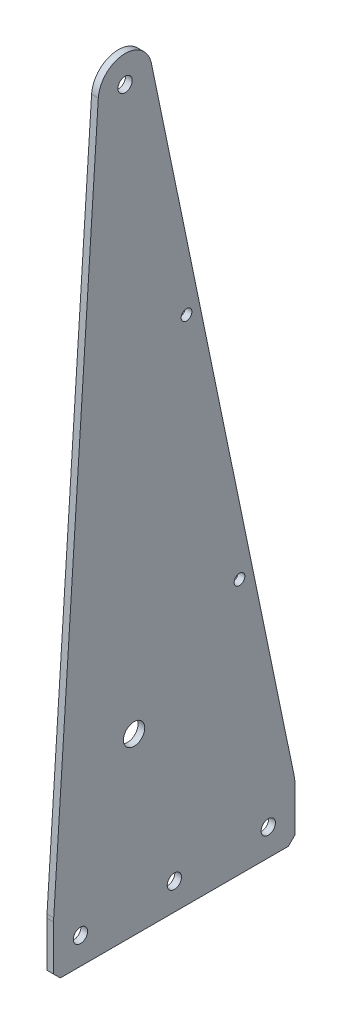
SolidWorks part; units mm, degrees
material "6061-T6 (SS)"
ref_plane "Front" through (0, 0, 0) normal (0, 0, 1) x (1, 0, 0)
ref_plane "Top" through (0, 0, 0) normal (0, 1, 0) x (1, 0, 0)
ref_plane "Right" through (0, 0, 0) normal (1, 0, 0) x (0, 0, -1)
sketch "Sketch1" plane through (0, 0, 0) normal (1, 0, 0) x (0, 0, -1)
  line L5 (63.5, 82.55) -> (-348.9452, 11.9126) construction
  line L6 (63.5, 82.55) -> (-7.1374, 494.9952) construction
  line L7 (59.2324, 350.8928) -> (22.2931, 141.3996) construction
  line L8 (22.2931, 141.3996) -> (4.6504, 41.3431) construction
  line L9 (63.5, 82.55) -> (4.6504, 41.3431) construction
  line L10 (4.6504, 41.3431) -> (-0.5288, 71.5841) construction
  line L11 (63.5, 82.55) -> (22.2931, 141.3996) construction
  line L12 (22.2931, 141.3996) -> (52.5341, 146.5788) construction
  circle A0 centre (63.5, 82.55) radius 5.0419
  dimension "D1" = 10.0838
  dimension "D3" = 63.5
  dimension "D2" = 82.55
  dimension "D4" = 80
  dimension "D7" = 70.6374
  dimension "D8" = 412.4452
  dimension "D9" = 90
  dimension "D10" = 101.6
  dimension "D11" = 212.725
sketch "Sketch2" plane through (0, 0, 0) normal (1, 0, 0) x (0, 0, -1)
  line L0 (25.4, 0) -> (25.4, 25.4)
  line L2 (25.4, 0) -> (139.7, 0)
  line L3 (139.7, 0) -> (139.7, 25.4)
  line L4 (139.7, 25.4) -> (71.6678, 353.4715)
  line L6 (25.4, 25.4) -> (46.559, 351.7146)
  arc A0 (71.6678, 353.4715) -> (46.559, 351.7146) centre (59.2324, 350.8928) ccw
  circle A2 centre (63.5, 82.55) radius 5.0419 construction
  circle A3 centre (63.5, 82.55) radius 5.0419
  circle A4 centre (59.2324, 350.8928) radius 3.3782
  dimension "D3" = 12.7
  dimension "D4" = 6.7564
  dimension "D5" = 25.4
  dimension "D1" = 25.4
  dimension "D2" = 139.7
extrude "Boss-Extrude2" add sketch "Sketch2" along normal blind 3.175
sketch "Sketch3" plane through (3.175, 0, 0) normal (1, 0, 0) x (0, 0, -1)
  line L0 (25.4, 0) -> (139.7, 0) construction
  line L1 (25.4, 25.4) -> (25.4, 0) construction
  line L2 (139.7, 0) -> (139.7, 25.4) construction
  line L3 (38.1, 12.7) -> (127, 12.7) construction
  line L4 (139.7, 25.4) -> (71.6678, 353.4715) construction
  line L5 (113.3937, 120.9839) -> (88.3053, 241.9677) construction
  line L6 (88.3053, 241.9677) -> (63.2169, 362.9516) construction
  line L7 (113.3937, 120.9839) -> (138.4821, 0) construction
  circle A0 centre (38.1, 12.7) radius 3.3782
  circle A1 centre (82.55, 12.7) radius 3.3782
  circle A2 centre (127, 12.7) radius 3.3782
  circle A3 centre (88.3053, 241.9677) radius 2.54
  circle A4 centre (113.3937, 120.9839) radius 2.54
  arc A5 (71.6678, 353.4715) -> (46.559, 351.7146) centre (59.2324, 350.8928) ccw construction
  dimension "D1" = 12.7
  dimension "D2" = 12.7
  dimension "D3" = 12.7
  dimension "D4" = 6.7564
  dimension "D5" = 6.35
  dimension "D6" = 6.35
  dimension "D7" = 5.08
extrude "Cut-Extrude1" cut sketch "Sketch3" against normal through all
chamfer "Chamfer1" distance 3.175 angle 45 2 edges at (1.5875, 0, -25.4) (1.5875, 0, -139.7)
fillet "Fillet1" radius 25.4 2 edges at (1.5875, 25.4, -139.7) (1.5875, 25.4, -25.4)
